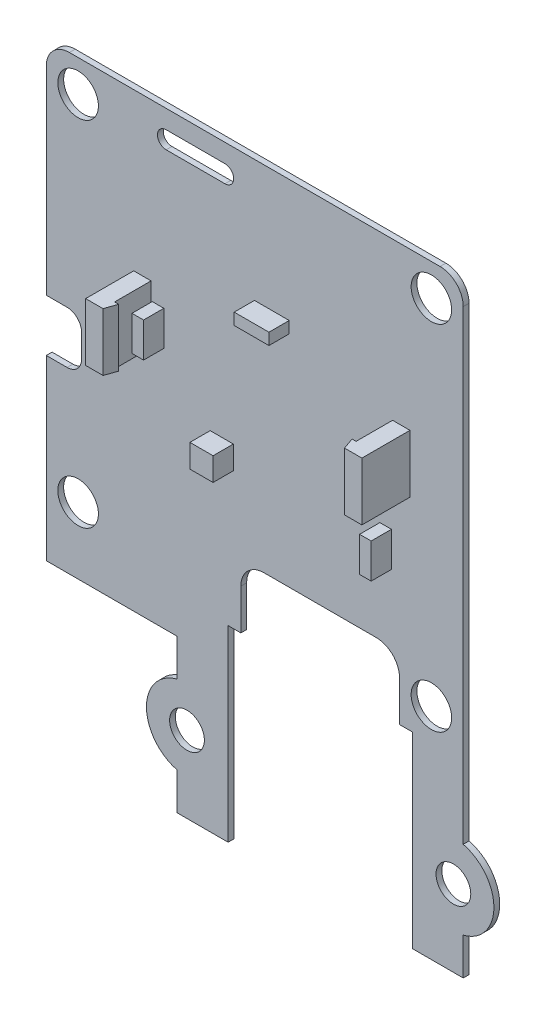
SolidWorks part; units mm, degrees
ref_plane "Front Plane" through (0, 0, 0) normal (0, 0, 1) x (1, 0, 0)
ref_plane "Top Plane" through (0, 0, 0) normal (0, 1, 0) x (1, 0, 0)
ref_plane "Right Plane" through (0, 0, 0) normal (1, 0, 0) x (0, 0, -1)
sketch "Sketch1" plane through (0, 0, 0) normal (0, 0, 1) x (1, 0, 0)
  line L1 (-14.95, -2.4) -> (-14.95, -4.4) construction
  line L2 (-16.2, -1.15) -> (-16.2, -5.65)
  line L3 (-14.95, -2.4) -> (-14.95, -4.4)
  line L4 (-7.65, 14.9) -> (-2.57, 14.9) construction
  line L5 (13.6, -18.1) -> (13.6, -34.2)
  line L6 (13.6, -34.2) -> (18, -34.2)
  line L7 (-2.3, -34.2) -> (-2.3, -18.1)
  line L8 (16, 18) -> (-16, 18)
  line L9 (-18, 16) -> (-18, -1.15)
  line L10 (-18, -18) -> (-1.2, -18)
  line L11 (-1.2, -18) -> (-1.2, -14.5)
  line L12 (0.8, -12.5) -> (10.5, -12.5)
  line L13 (12.5, -14.5) -> (12.5, -18)
  line L14 (12.5, -18) -> (18, -18)
  line L15 (18, -18) -> (18, 16)
  line L16 (16, 18) -> (-16, 18)
  line L17 (-18, 16) -> (-18, -1.15)
  line L18 (-18, -18) -> (-1.2, -18)
  line L19 (-1.2, -18) -> (-1.2, -14.5)
  line L20 (0.8, -12.5) -> (10.5, -12.5)
  line L21 (12.5, -14.5) -> (12.5, -18)
  line L22 (12.5, -18) -> (18, -18)
  line L23 (18, -18) -> (18, 16)
  line L24 (-2.3, -18.1) -> (-18, -18.1)
  line L25 (-18, -18.1) -> (-18, -21)
  line L26 (-18, -21) -> (-6.7, -21)
  line L27 (-6.7, -21) -> (-6.7, -24.2048)
  line L28 (-6.7, -30.9952) -> (-6.7, -34.2)
  line L29 (-6.7, -34.2) -> (-2.3, -34.2)
  line L30 (-2.3, -34.2) -> (-2.3, -18.1)
  line L31 (-2.3, -18.1) -> (-18, -18.1)
  line L32 (-18, -18.1) -> (-18, -21)
  line L33 (-18, -21) -> (-6.7, -21)
  line L34 (-6.7, -21) -> (-6.7, -24.2048)
  line L35 (-6.7, -30.9952) -> (-6.7, -34.2)
  line L36 (-6.7, -34.2) -> (-2.3, -34.2)
  line L37 (18, -34.2) -> (18, -30.9952)
  line L38 (18, -24.2048) -> (18, -18.1)
  line L39 (18, -18.1) -> (13.6, -18.1)
  line L40 (13.6, -18.1) -> (13.6, -34.2)
  line L41 (13.6, -34.2) -> (18, -34.2)
  line L42 (18, -34.2) -> (18, -30.9952)
  line L43 (18, -24.2048) -> (18, -18.1)
  line L44 (18, -18.1) -> (13.6, -18.1)
  line L45 (-7.65, 16.4) -> (-2.57, 16.4) construction
  line L46 (-7.65, 14.9) -> (-2.57, 14.9)
  line L47 (-7.65, 16.4) -> (-2.57, 16.4)
  line L48 (-18, -1.15) -> (-18, -18.1)
  line L49 (18, -18) -> (18, -18.1)
  line L50 (13.6, -18.1) -> (13.6, -18)
  line L51 (-2.3, -18.1) -> (-2.3, -18)
  line L112 (-18, -1.15) -> (-16.2, -1.15)
  line L113 (-18, -1.15) -> (-16.2, -1.15)
  line L114 (-14.95, -2.4) -> (-14.95, -4.4)
  line L115 (-14.95, -2.4) -> (-14.95, -4.4)
  line L116 (-16.2, -5.65) -> (-18, -5.65)
  line L117 (-16.2, -5.65) -> (-18, -5.65)
  line L118 (-18, -5.65) -> (-18, -18)
  line L119 (-18, -5.65) -> (-18, -18)
  arc A0 (-16.2, -5.65) -> (-14.95, -4.4) centre (-16.2, -4.4) ccw construction
  arc A1 (-6.7, -24.2048) -> (-6.7, -30.9952) centre (-5.85, -27.6) ccw
  arc A2 (-6.7, -24.2048) -> (-6.7, -30.9952) centre (-5.85, -27.6) ccw
  arc A3 (18, -30.9952) -> (18, -24.2048) centre (17.15, -27.6) ccw
  arc A4 (-16, 18) -> (-18, 16) centre (-16, 16) ccw
  arc A5 (0.8, -12.5) -> (-1.2, -14.5) centre (0.8, -14.5) ccw
  arc A6 (12.5, -14.5) -> (10.5, -12.5) centre (10.5, -14.5) ccw
  arc A7 (18, 16) -> (16, 18) centre (16, 16) ccw
  arc A8 (-16, 18) -> (-18, 16) centre (-16, 16) ccw
  arc A9 (0.8, -12.5) -> (-1.2, -14.5) centre (0.8, -14.5) ccw
  arc A10 (12.5, -14.5) -> (10.5, -12.5) centre (10.5, -14.5) ccw
  arc A11 (18, 16) -> (16, 18) centre (16, 16) ccw
  arc A12 (18, -30.9952) -> (18, -24.2048) centre (17.15, -27.6) ccw
  arc A13 (-14.95, -2.4) -> (-16.2, -1.15) centre (-16.2, -2.4) ccw construction
  arc A14 (-16.2, -5.65) -> (-14.95, -4.4) centre (-16.2, -4.4) ccw
  arc A15 (-14.95, -2.4) -> (-16.2, -1.15) centre (-16.2, -2.4) ccw
  circle A18 centre (17.15, -27.6) radius 1.5 construction
  circle A19 centre (-5.85, -27.6) radius 1.5 construction
  circle A22 centre (15.25, 15.25) radius 1.75
  circle A23 centre (15.25, -15.25) radius 1.75
  circle A24 centre (17.15, -27.6) radius 1.5
  circle A25 centre (-5.85, -27.6) radius 1.5
  circle A26 centre (-15.25, -15.25) radius 1.75
  circle A27 centre (-15.25, 15.25) radius 1.75
  arc A28 (-2.57, 14.9) -> (-2.57, 16.4) centre (-2.57, 15.65) ccw construction
  arc A29 (-7.65, 16.4) -> (-7.65, 14.9) centre (-7.65, 15.65) ccw construction
  arc A30 (-2.57, 14.9) -> (-2.57, 16.4) centre (-2.57, 15.65) ccw
  arc A31 (-7.65, 16.4) -> (-7.65, 14.9) centre (-7.65, 15.65) ccw
  circle A46 centre (15.25, -15.25) radius 1.75 construction
  circle A47 centre (-15.25, -15.25) radius 1.75 construction
  circle A48 centre (-15.25, 15.25) radius 1.75 construction
  circle A49 centre (15.25, 15.25) radius 1.75 construction
  arc A62 (-14.95, -2.4) -> (-16.2, -1.15) centre (-16.2, -2.4) ccw
  arc A63 (-14.95, -2.4) -> (-16.2, -1.15) centre (-16.2, -2.4) ccw
  arc A64 (-16.2, -5.65) -> (-14.95, -4.4) centre (-16.2, -4.4) ccw
  arc A65 (-16.2, -5.65) -> (-14.95, -4.4) centre (-16.2, -4.4) ccw
  dimension "D1" = 0
  dimension "D2" = 0
  dimension "D3" = 0
extrude "Base shape" add sketch "Sketch1" along normal blind 0.5 contours L23 A11 L16 A8 L17 L18 L19 A9 L20 A10 L21 L22 A31 L47 A30 L46 A27 A26 A23 A22 A15 L3 A14 L2 | L31 L51 L18 L48 | L34 A2 L35 L36 L30 L31 L32 L33 A25 | L50 L44 L49 L22 | L42 A12 L43 L44 L40 L41 A24 region at (-0.1312, 0.8573, 0) region at (-10.15, -18.05, 0) region at (-10.15, -18.3249, 0) region at (15.8, -18.05, 0) region at (16.2483, -26.2681, 0)
sketch "Sketch2" plane through (0, 0, 0.5) normal (0, 0, 1) x (1, 0, 0)
  line L0 (1.475, 16.95) -> (1.475, -13.05) construction
  line L1 (-7.85, 1.45) -> (-8.85, 1.45) construction
  line L2 (-0.025, 7.45) -> (2.975, 7.45)
  line L3 (-0.025, 7.45) -> (-0.025, 6.45)
  line L4 (11.8, 16.95) -> (-8.85, 16.95)
  line L5 (-8.85, 16.95) -> (-8.85, -13.05)
  line L6 (-8.85, -13.05) -> (11.8, -13.05)
  line L7 (11.8, -13.05) -> (11.8, 16.95)
  line L8 (11.8, 16.95) -> (-8.85, 16.95)
  line L9 (-8.85, 16.95) -> (-8.85, -13.05)
  line L10 (-8.85, -13.05) -> (11.8, -13.05)
  line L11 (11.8, -13.05) -> (11.8, 16.95)
  line L12 (-0.025, 6.45) -> (2.975, 6.45)
  line L13 (2.975, 7.45) -> (2.975, 6.45)
  line L14 (-0.025, 7.45) -> (2.975, 6.45) construction
  line L15 (-0.025, 6.45) -> (2.975, 7.45) construction
  line L16 (-8.85, 2.95) -> (-7.85, 2.95)
  line L17 (-8.85, 2.95) -> (-8.85, -0.05)
  line L18 (-8.85, -0.05) -> (-7.85, -0.05)
  line L19 (-7.85, 2.95) -> (-7.85, -0.05)
  line L20 (-3.85, -4.2) -> (-1.85, -4.2)
  line L21 (-3.85, -4.2) -> (-3.85, -6.2)
  line L22 (-3.85, -6.2) -> (-1.85, -6.2)
  line L23 (-1.85, -4.2) -> (-1.85, -6.2)
  line L24 (11.8, -3.75) -> (10.8, -3.75)
  line L25 (11.8, -3.75) -> (11.8, -6.75)
  line L26 (11.8, -6.75) -> (10.8, -6.75)
  line L27 (10.8, -3.75) -> (10.8, -6.75)
  line L28 (11.8, 1.95) -> (10.8, 1.95)
  line L29 (11.8, 1.95) -> (11.8, -1.05)
  line L30 (11.8, -1.05) -> (10.8, -1.05)
  line L31 (10.8, 1.95) -> (10.8, -1.05)
  line L32 (-3.85, -5.2) -> (-1.85, -5.2) construction
  line L33 (-2.85, -4.2) -> (-2.85, -6.2) construction
  line L34 (10.8, 0.45) -> (11.8, 0.45) construction
  line L35 (10.8, -5.25) -> (11.8, -5.25) construction
  point P6 (1.475, 6.95)
  dimension "D2" = 3
  dimension "D3" = 1
  dimension "D4" = 10
  dimension "D5" = 7.8
  dimension "D6" = 16.5
  dimension "D7" = 7.85
  dimension "D8" = 6
  dimension "D9" = 2
  dimension "D10" = 15.5
  dimension "D1" = 0
extrude "RX supports" add sketch "Sketch2" along normal blind 1.75 contours L13 L2 L3 L12 | L19 L16 L9 L18 | L23 L20 L21 L22 | L28 L31 L30 L11 | L24 L27 L26 L11 region at (1.475, 6.95, 0.5) region at (11.3, 0.45, 0.5) region at (-8.35, 1.45, 0.5) region at (11.3, -5.25, 0.5) region at (-2.85, -5.2, 0.5)
sketch "Sketch3" plane through (0, 0, 0.5) normal (0, 0, 1) x (1, 0, 0)
  line L0 (-8.85, 1.95) -> (11.8, 1.95) construction
  line L1 (1.475, 16.95) -> (1.475, -13.05) construction
  line L2 (-8.95, 4.45) -> (-10.45, 4.45)
  line L3 (-8.95, 4.45) -> (-8.95, -0.55)
  line L4 (11.8, 16.95) -> (-8.85, 16.95)
  line L5 (-8.85, 16.95) -> (-8.85, -13.05)
  line L6 (-8.85, -13.05) -> (11.8, -13.05)
  line L7 (11.8, -13.05) -> (11.8, 16.95)
  line L8 (11.8, 16.95) -> (-8.85, 16.95)
  line L9 (-8.85, 16.95) -> (-8.85, -13.05)
  line L10 (-8.85, -13.05) -> (11.8, -13.05)
  line L11 (11.8, -13.05) -> (11.8, 16.95)
  line L12 (-8.95, -0.55) -> (-10.45, -0.55)
  line L13 (-10.45, 4.45) -> (-10.45, -0.55)
  line L14 (11.9, -0.55) -> (13.4, -0.55)
  line L15 (13.4, 4.45) -> (13.4, -0.55)
  line L16 (11.9, 4.45) -> (13.4, 4.45)
  line L17 (11.9, 4.45) -> (11.9, -0.55)
  point P10 (-10.45, 1.95)
  dimension "D2" = 5
  dimension "D3" = 1.5
  dimension "D4" = 0.1
  dimension "D1" = 0
extrude "Clip base" add sketch "Sketch3" along normal offset from surface (3.15 mm away) 0.2 contours L2 L13 L12 L3 | L16 L17 L14 L15 region at (-9.7, 1.95, 0.5) region at (12.65, 1.95, 0.5) offset beyond the face yes
sketch "Sketch4" plane through (0, 0, 3.65) normal (0, 0, 1) x (1, 0, 0)
  line L0 (-8.95, -0.55) -> (-10.45, -0.55) construction
  line L1 (-10.45, 4.45) -> (-8.6, 4.45)
  line L2 (-10.45, 4.45) -> (-10.45, -0.55)
  line L3 (-10.45, -0.55) -> (-8.6, -0.55)
  line L4 (-8.6, 4.45) -> (-8.6, -0.55)
  line L5 (-8.95, 4.45) -> (-8.95, -0.55) construction
  line L6 (-10.45, 1.95) -> (13.4, 1.95) construction
  line L7 (13.4, 4.45) -> (13.4, -0.55) construction
  line L8 (1.475, 4.45) -> (1.475, -0.55) construction
  line L9 (11.55, 4.45) -> (11.55, -0.55)
  line L10 (13.4, 4.45) -> (11.55, 4.45)
  line L11 (13.4, 4.45) -> (13.4, -0.55)
  line L12 (13.4, -0.55) -> (11.55, -0.55)
  point P17 (1.475, 1.95)
  dimension "D1" = 0.35
extrude "Clip top" add sketch "Sketch4" along normal blind 1
sketch "Sketch5" plane through (0, -0.55, 0) normal (0, -1, 0) x (1, 0, 0)
  line L0 (-8.6, 3.65) -> (-8.95, 4.65)
  line L1 (-10.45, 4.65) -> (-8.6, 4.65) construction
  line L2 (-8.95, 4.65) -> (-8.6, 4.65)
  line L3 (-8.6, 4.65) -> (-8.6, 3.65)
  line L4 (-8.95, 3.65) -> (-8.95, 0.5) construction
  line L5 (11.55, 3.65) -> (11.9, 4.65)
  line L6 (11.55, 4.65) -> (13.4, 4.65) construction
  line L7 (11.9, 4.65) -> (11.55, 4.65)
  line L8 (11.55, 4.65) -> (11.55, 3.65)
  line L9 (11.9, 3.65) -> (11.9, 0.5) construction
extrude "Clip chamfer" cut sketch "Sketch5" against normal up to next
